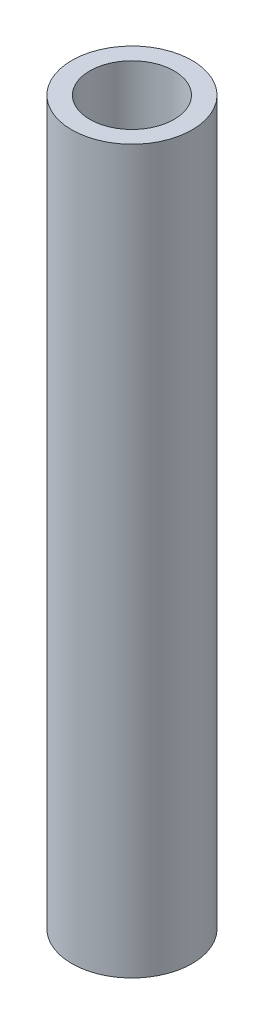
SolidWorks part; units mm, degrees
material "PVC Rigid"
ref_plane "Front Plane" through (0, 0, 0) normal (0, 0, 1) x (1, 0, 0)
ref_plane "Top Plane" through (0, 0, 0) normal (0, 1, 0) x (1, 0, 0)
ref_plane "Right Plane" through (0, 0, 0) normal (1, 0, 0) x (0, 0, -1)
sketch "Feed Tube Sketch" plane through (0, 0, 0) normal (0, 1, 0) x (1, 0, 0)
  circle A0 centre (0, 0) radius 10
  circle A1 centre (0, 0) radius 7
  dimension "D1" = 20
  dimension "D2" = 14
extrude "Feed Tube" add sketch "Feed Tube Sketch" along normal blind 120
